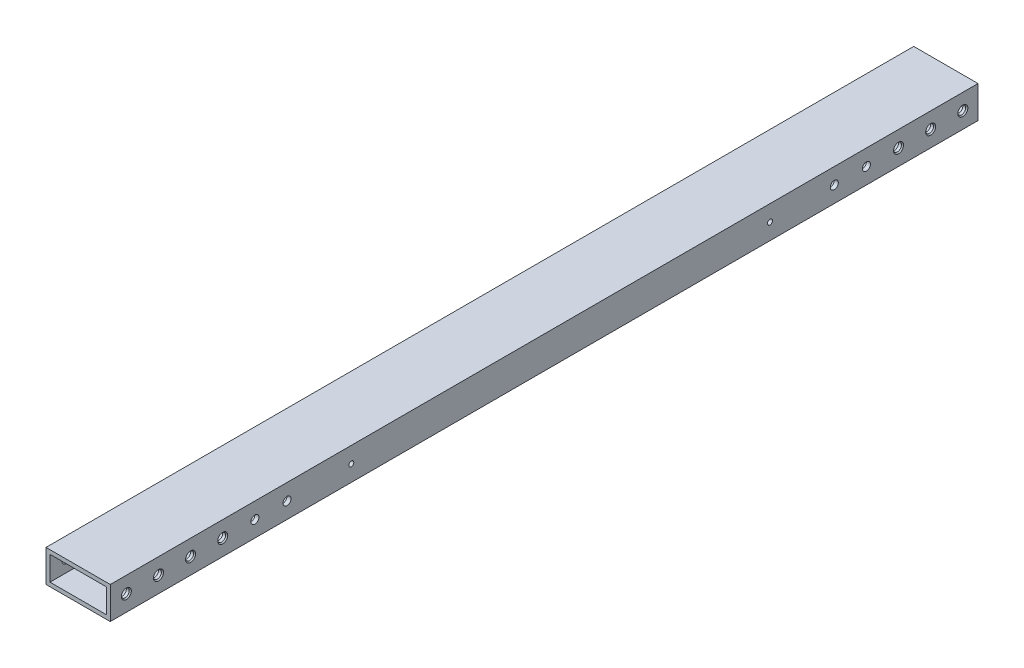
SolidWorks part; units mm, degrees
material "6061 Alloy"
ref_plane "Front Plane" through (0, 0, 0) normal (0, 0, 1) x (1, 0, 0)
ref_plane "Top Plane" through (0, 0, 0) normal (0, 1, 0) x (1, 0, 0)
ref_plane "Right Plane" through (0, 0, 0) normal (1, 0, 0) x (0, 0, -1)
sketch "Sketch1" plane through (0, 0, 0) normal (0, 0, 1) x (1, 0, 0)
  line L0 (-22.225, 9.525) -> (22.225, 9.525)
  line L2 (-25.4, 12.7) -> (25.4, 12.7)
  line L3 (-25.4, 12.7) -> (-25.4, -12.7)
  line L4 (-25.4, -12.7) -> (25.4, -12.7)
  line L5 (25.4, 12.7) -> (25.4, -12.7)
  line L10 (22.225, 9.525) -> (22.225, -9.525)
  line L11 (-22.225, -9.525) -> (22.225, -9.525)
  line L12 (-22.225, 9.525) -> (-22.225, -9.525)
  point P12 (0, 12.7)
  point P14 (25.4, 0)
  dimension "Wall Thickness" = 3.175
  dimension "Outside Width" = 50.8
  dimension "Outside Height" = 25.4
  dimension "Inside Height" = 19.05
  dimension "Inside Width" = 44.45
sketch "Sketch2" plane through (0, 0, 0) normal (1, 0, 0) x (0, 0, -1)
  line L0 (342.9, 0) -> (-342.9, 0)
  point P4 (0, 0)
  point P7 (-342.9, 0)
  point P10 (342.9, 0)
  dimension "Length" = 685.8
sketch "Sketch3" plane through (0, 0, 0) normal (0, 0, 1) x (1, 0, 0)
  line L21 (25.4, 12.7) -> (-25.4, 12.7)
  line L22 (25.4, -12.7) -> (25.4, 12.7)
  line L23 (-25.4, -12.7) -> (25.4, -12.7)
  line L24 (-25.4, 12.7) -> (-25.4, -12.7)
  line L25 (25.4, 12.7) -> (-25.4, 12.7)
  line L26 (25.4, -12.7) -> (25.4, 12.7)
  line L27 (-25.4, -12.7) -> (25.4, -12.7)
  line L28 (-25.4, 12.7) -> (-25.4, -12.7)
  line L29 (22.225, 9.525) -> (-22.225, 9.525)
  line L30 (22.225, -9.525) -> (22.225, 9.525)
  line L31 (-22.225, -9.525) -> (22.225, -9.525)
  line L32 (-22.225, 9.525) -> (-22.225, -9.525)
  line L33 (22.225, 9.525) -> (-22.225, 9.525)
  line L34 (22.225, -9.525) -> (22.225, 9.525)
  line L35 (-22.225, -9.525) -> (22.225, -9.525)
  line L36 (-22.225, 9.525) -> (-22.225, -9.525)
  dimension "D1" = 0
  dimension "D2" = 0
extrude "Boss-Extrude1" add sketch "Sketch3" along normal up to vertex (342.9 mm away) and the other way up to vertex (342.9 mm away) up to point (0, 0, 342.9) other way up to point (0, 0, -342.9)
sketch "Drawing Reference" plane through (0, 0, 0) normal (1, 0, 0) x (0, 0, -1)
  line L0 (-342.9, 0) -> (342.9, 0) construction
  line L1 (0, -12.7) -> (0, 12.7) construction
  line L2 (-342.9, -12.7) -> (342.9, -12.7) construction
  line L5 (-342.9, 12.7) -> (342.9, 12.7) construction
  point P7 (-306.324, 0)
  point P8 (306.324, 0)
  dimension "D1" = 36.576
sketch "Sketch5" plane through (25.4, 0, 0) normal (1, 0, 0) x (0, 0, -1)
  line L0 (-342.9, 0) -> (-279.4, 0)
  line L1 (-342.9, -12.7) -> (-342.9, 12.7) construction
  line L2 (-279.4, 0) -> (-254, 0)
  line L3 (-254, 0) -> (-228.6, 0)
  line L4 (-228.6, 0) -> (-203.2, 0)
sketch "Sketch8" plane through (25.4, 0, 0) normal (1, 0, 0) x (0, 0, -1)
  line L0 (342.9, 0) -> (305.5118, 0)
  line L1 (342.9, -12.7) -> (342.9, 12.7) construction
  line L2 (305.5118, 0) -> (280.1118, 0)
  line L3 (280.1118, 0) -> (254.7118, 0)
  line L4 (254.7118, 0) -> (229.3118, 0)
hole_wizard "1/4 (0.25) Diameter Hole3" positions "Sketch12" profile "Sketch13" hole size "1/4" standard "ANSI Inch" end condition through all
sketch "Sketch12" plane through (-25.4, 0, 0) normal (-1, 0, 0) x (0, 0, 1)
  point P0 (-330.9118, 0)
sketch "Sketch13" plane through (-25.4, 0, -330.9118) normal (0, 1, 0) x (0, 0, 1)
  line L0 (0, 0) -> (0, 50.8)
  line L1 (0, 50.8) -> (3.9624, 50.8)
  line L2 (3.175, 49.8942) -> (3.175, 0)
  line L5 (3.175, 0) -> (0, 0)
  line L7 (3.9624, 50.8) -> (3.175, 49.8942)
  line L8 (-3.9624, 50.8) -> (-3.175, 49.8942) construction
  line L11 (0, -6.35) -> (0, 107.95) construction
  dimension "Thru Hole Dia." = 6.35
  dimension "Thru Hole Depth" = 50.8
  dimension "Far C'Sink Dia." = 7.9248
  dimension "Far C'Sink Angle" = 82
hole_wizard "1/4 (0.25) Diameter Hole4" positions "Sketch14" profile "Sketch15" hole size "1/4" standard "ANSI Inch" end condition through all
sketch "Sketch14" plane through (-25.4, 0, 0) normal (-1, 0, 0) x (0, 0, 1)
  point P0 (304.8, 0)
  point P3 (330.2, 0)
sketch "Sketch15" plane through (-25.4, 0, 304.8) normal (0, 1, 0) x (0, 0, 1)
  line L0 (0, 0) -> (0, 50.8)
  line L1 (0, 50.8) -> (3.9624, 50.8)
  line L2 (3.175, 49.8942) -> (3.175, 0)
  line L5 (3.175, 0) -> (0, 0)
  line L7 (3.9624, 50.8) -> (3.175, 49.8942)
  line L8 (-3.9624, 50.8) -> (-3.175, 49.8942) construction
  line L11 (0, -6.35) -> (0, 107.95) construction
  dimension "Thru Hole Dia." = 6.35
  dimension "Thru Hole Depth" = 50.8
  dimension "Far C'Sink Dia." = 7.9248
  dimension "Far C'Sink Angle" = 82
hole_wizard "1/4 (0.25) Diameter Hole5" positions "Sketch17" profile "Sketch18" hole size "1/4" standard "ANSI Inch" end condition through all
sketch "Sketch17" plane through (25.4, 0, 0) normal (1, 0, 0) x (0, 0, -1)
  point P0 (305.5118, 0)
  point P3 (280.1118, 0)
sketch "Sketch18" plane through (25.4, 0, -305.5118) normal (0, 1, 0) x (0, 0, -1)
  line L0 (0, 0) -> (0, 50.8)
  line L1 (0, 50.8) -> (3.175, 50.8)
  line L2 (3.175, 50.8) -> (3.175, 0.9058)
  line L3 (3.175, 0.9058) -> (3.9624, 0)
  line L5 (3.9624, 0) -> (0, 0)
  line L6 (-3.175, 0.9058) -> (-3.9624, 0) construction
  line L11 (0, -6.35) -> (0, 107.95) construction
  dimension "Thru Hole Dia." = 6.35
  dimension "Thru Hole Depth" = 50.8
  dimension "Near C'Sink Dia." = 7.9248
  dimension "Near C'Sink Angle" = 82
hole_wizard "1/4 (0.25) Diameter Hole6" positions "Sketch19" profile "Sketch20" hole size "1/4" standard "ANSI Inch" end condition through all
sketch "Sketch19" plane through (25.4, 0, 0) normal (1, 0, 0) x (0, 0, -1)
  point P0 (229.3118, 0)
  point P3 (254.7118, 0)
sketch "Sketch20" plane through (25.4, 0, -229.3118) normal (0, 1, 0) x (0, 0, -1)
  line L0 (0, 0) -> (0, 50.8)
  line L1 (0, 50.8) -> (3.175, 50.8)
  line L2 (3.175, 50.8) -> (3.175, 0)
  line L5 (3.175, 0) -> (0, 0)
  line L11 (0, -6.35) -> (0, 107.95) construction
  dimension "Thru Hole Dia." = 6.35
  dimension "Thru Hole Depth" = 50.8
hole_wizard "1/4 (0.25) Diameter Hole7" positions "Sketch21" profile "Sketch22" hole size "1/4" standard "ANSI Inch" end condition through all
sketch "Sketch21" plane through (25.4, 0, 0) normal (1, 0, 0) x (0, 0, -1)
  point P0 (-203.2, 0)
  point P3 (-228.6, 0)
sketch "Sketch22" plane through (25.4, 0, 203.2) normal (0, 1, 0) x (0, 0, -1)
  line L0 (0, 0) -> (0, 50.8)
  line L1 (0, 50.8) -> (3.175, 50.8)
  line L2 (3.175, 50.8) -> (3.175, 0)
  line L5 (3.175, 0) -> (0, 0)
  line L11 (0, -6.35) -> (0, 107.95) construction
  dimension "Thru Hole Dia." = 6.35
  dimension "Thru Hole Depth" = 50.8
hole_wizard "1/4 (0.25) Diameter Hole8" positions "Sketch23" profile "Sketch24" hole size "1/4" standard "ANSI Inch" end condition through all
sketch "Sketch23" plane through (25.4, 0, 0) normal (1, 0, 0) x (0, 0, -1)
  point P0 (-279.4, 0)
  point P3 (-254, 0)
sketch "Sketch24" plane through (25.4, 0, 279.4) normal (0, 1, 0) x (0, 0, -1)
  line L0 (0, 0) -> (0, 50.8)
  line L1 (0, 50.8) -> (3.175, 50.8)
  line L2 (3.175, 50.8) -> (3.175, 0.9058)
  line L3 (3.175, 0.9058) -> (3.9624, 0)
  line L5 (3.9624, 0) -> (0, 0)
  line L6 (-3.175, 0.9058) -> (-3.9624, 0) construction
  line L11 (0, -6.35) -> (0, 107.95) construction
  dimension "Thru Hole Dia." = 6.35
  dimension "Thru Hole Depth" = 50.8
  dimension "Near C'Sink Dia." = 7.9248
  dimension "Near C'Sink Angle" = 82
sketch "Sketch25" plane through (25.4, 0, 0) normal (1, 0, 0) x (0, 0, -1)
  line L0 (-203.2, 0) -> (-152.4, 0)
  line L1 (229.3118, 0) -> (178.5118, 0)
hole_wizard "5/32 (0.15625) Diameter Hole1" positions "Sketch26" profile "Sketch27" hole size "5/32" standard "ANSI Inch" end condition through all
sketch "Sketch26" plane through (25.4, 0, 0) normal (1, 0, 0) x (0, 0, -1)
  point P0 (-152.4, 0)
  point P3 (178.5118, 0)
sketch "Sketch27" plane through (25.4, 0, 152.4) normal (0, 1, 0) x (0, 0, -1)
  line L0 (0, 0) -> (0, 50.8)
  line L1 (0, 50.8) -> (1.9844, 50.8)
  line L2 (1.9844, 50.8) -> (1.9844, 0)
  line L5 (1.9844, 0) -> (0, 0)
  line L11 (0, -6.35) -> (0, 107.95) construction
  dimension "Thru Hole Dia." = 3.9688
  dimension "Thru Hole Depth" = 50.8
sketch "Sketch30" plane through (-25.4, 0, 0) normal (-1, 0, 0) x (0, 0, 1)
  point P0 (-128.9434, 0.355)
  point P1 (-103.5434, 0.3445)
  point P2 (77.4316, 0.355)
  point P3 (102.8316, 0.355)
hole_wizard "1/2 (0.5) Diameter Hole1" positions "Sketch33" profile "Sketch34" hole size "1/2" standard "ANSI Inch"
sketch "Sketch33" plane through (-25.4, 0, 0) normal (-1, 0, 0) x (0, 0, 1)
  point P0 (-128.9434, 0.355)
  point P3 (-103.5434, 0.3445)
  point P7 (77.4316, 0.355)
  point P10 (102.8316, 0.355)
sketch "Sketch34" plane through (-25.4, 0.355, -128.9434) normal (0, 1, 0) x (0, 0, 1)
  line L0 (0, 0) -> (0, 10.1655)
  line L1 (0, 10.1655) -> (6.35, 6.35)
  line L2 (6.35, 6.35) -> (6.35, 0)
  line L5 (6.35, 0) -> (0, 0)
  line L10 (0, 10.1655) -> (-6.35, 6.35) construction
  line L11 (0, -6.35) -> (0, 107.95) construction
  dimension "Hole Dia." = 12.7
  dimension "Hole Depth" = 6.35
  dimension "Drill Angle" = 118
equation "\"D1@Drawing Reference\"=\"Outside Width@Sketch1\" * 0.72"
